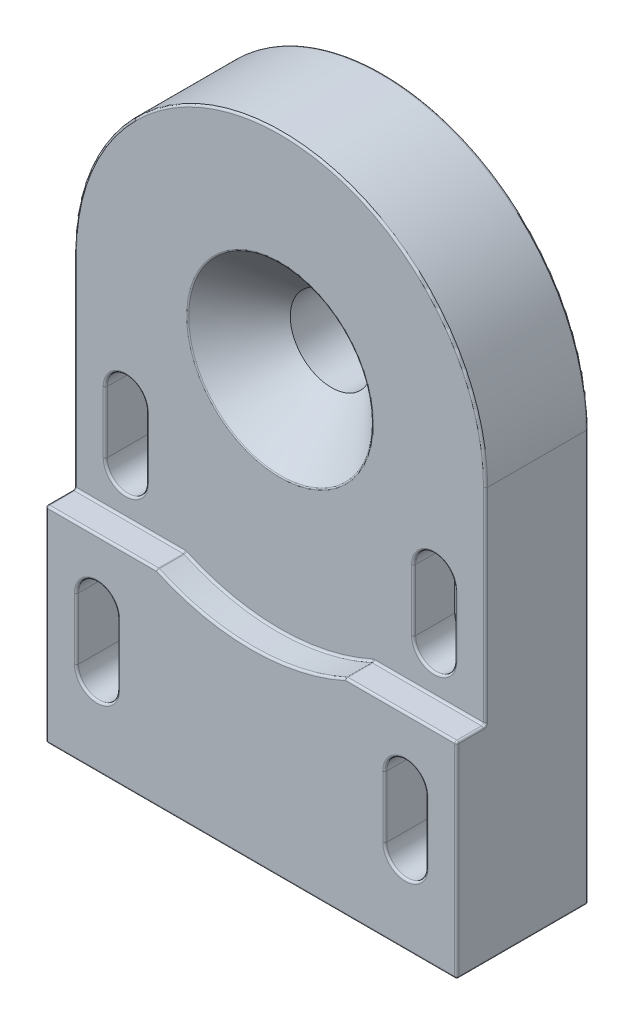
SolidWorks part; units mm, degrees
ref_plane "Front Plane" through (0, 0, 0) normal (0, 0, 1) x (1, 0, 0)
ref_plane "Top Plane" through (0, 0, 0) normal (0, 1, 0) x (1, 0, 0)
ref_plane "Right Plane" through (0, 0, 0) normal (1, 0, 0) x (0, 0, -1)
sketch "Sketch1" plane through (0, 0, 0) normal (0, 0, 1) x (1, 0, 0)
  line L0 (-7.5, -13) -> (-7.5, -16) construction
  line L1 (-10, -20) -> (10, -20)
  line L2 (-10, -20) -> (-10, 10)
  line L4 (10, -20) -> (10, 10)
  line L5 (-6.5, -13) -> (-6.5, -16)
  line L6 (-8.5, -13) -> (-8.5, -16)
  line L7 (0, 10) -> (0, -20) construction
  line L8 (7.5, -13) -> (7.5, -16) construction
  line L11 (6.5, -13) -> (6.5, -16)
  line L12 (8.5, -13) -> (8.5, -16)
  line L23 (-10, 10) -> (10, 10)
  line L24 (-8.5, -5) -> (-8.5, -8)
  line L29 (-6.5, -5) -> (-6.5, -8)
  line L30 (6.5, -5) -> (6.5, -8)
  line L31 (8.5, -5) -> (8.5, -8)
  line L32 (-7.5, -5) -> (-7.5, -8) construction
  line L33 (7.5, -5) -> (7.5, -8) construction
  circle A1 centre (0, 0) radius 2
  arc A2 (-6.5, -13) -> (-8.5, -13) centre (-7.5, -13) ccw
  arc A3 (-8.5, -16) -> (-6.5, -16) centre (-7.5, -16) ccw
  arc A6 (6.5, -13) -> (8.5, -13) centre (7.5, -13) cw
  arc A7 (8.5, -16) -> (6.5, -16) centre (7.5, -16) cw
  arc A8 (-6.5, -5) -> (-8.5, -5) centre (-7.5, -5) ccw
  arc A9 (-8.5, -8) -> (-6.5, -8) centre (-7.5, -8) ccw
  arc A10 (8.5, -8) -> (6.5, -8) centre (7.5, -8) cw
  arc A11 (6.5, -5) -> (8.5, -5) centre (7.5, -5) cw
  point P0 (0, 0)
  point P10 (-7.5, -14.5)
  point P16 (-7.5, -12)
  point P17 (-7.5, -17)
  point P19 (7.5, -14.5)
  point P25 (7, 0.509)
  point P26 (-7.5, -6.5)
  point P36 (7.5, -6.5)
  dimension "D1" = 4
  dimension "D6" = 5
  dimension "D2" = 20
  dimension "D3" = 30
  dimension "D4" = 20
  dimension "D5" = 2
  dimension "D7" = 1.5
  dimension "D8" = 4
  dimension "D9" = 10
  dimension "D10" = 2
  dimension "D11" = 8
extrude "Boss-Extrude1" add sketch "Sketch1" along normal blind 5
chamfer "Chamfer1" distance 2.5 angle 45 1 edges at (2, 0, 5)
sketch "Sketch2" plane through (0, 0, 5) normal (0, 0, 1) x (1, 0, 0)
  line L0 (10, -20) -> (10, 10) construction
  line L1 (-10, -20) -> (10, -20)
  line L2 (-10, -20) -> (-10, -10)
  line L3 (-10, -10) -> (-4.5826, -10)
  line L4 (10, -20) -> (10, -10)
  line L7 (-8.5, -13) -> (-8.5, -16) construction
  line L8 (-6.5, -16) -> (-6.5, -13) construction
  line L11 (-8.5, -13) -> (-8.5, -16)
  line L12 (-6.5, -16) -> (-6.5, -13)
  line L13 (4.5826, -10) -> (10, -10)
  line L14 (8.5, -16) -> (8.5, -13) construction
  line L15 (6.5, -13) -> (6.5, -16) construction
  line L16 (8.5, -16) -> (8.5, -13)
  line L17 (6.5, -13) -> (6.5, -16)
  arc A2 (-8.5, -16) -> (-6.5, -16) centre (-7.5, -16) ccw construction
  arc A3 (-6.5, -13) -> (-8.5, -13) centre (-7.5, -13) ccw construction
  arc A6 (-8.5, -16) -> (-6.5, -16) centre (-7.5, -16) ccw
  arc A7 (-6.5, -13) -> (-8.5, -13) centre (-7.5, -13) ccw
  arc A9 (-4.5826, -10) -> (4.5826, -10) centre (0, 0) ccw
  arc A10 (6.5, -16) -> (8.5, -16) centre (7.5, -16) ccw construction
  arc A11 (8.5, -13) -> (6.5, -13) centre (7.5, -13) ccw construction
  arc A12 (6.5, -16) -> (8.5, -16) centre (7.5, -16) ccw
  arc A13 (8.5, -13) -> (6.5, -13) centre (7.5, -13) ccw
  circle A14 centre (0, 0) radius 4.5 construction
  point P10 (0, -2)
  point P15 (0, 0)
  point P28 (0, -11)
  dimension "D2" = 1
  dimension "D1" = 10
extrude "Boss-Extrude2" add sketch "Sketch2" along normal blind 1.4
sketch "Sketch3" plane through (0, 0, 0) normal (0, 0, -1) x (-1, 0, 0)
  line L0 (-7.5, -12) -> (7.5, -12)
  line L1 (7.5, -17) -> (-7.5, -17)
  line L2 (8.5, -13) -> (8.5, -16) construction
  line L4 (8.5, -13) -> (8.5, -16)
  line L6 (-8.5, -16) -> (-8.5, -13) construction
  line L7 (-8.5, -16) -> (-8.5, -13)
  line L8 (-8.5, -8) -> (-8.5, -5)
  line L9 (-7.5, -4) -> (7.5, -4)
  line L10 (8.5, -5) -> (8.5, -8)
  line L11 (7.5, -9) -> (-7.5, -9)
  arc A0 (-7.5, -4) -> (-8.5, -5) centre (-7.5, -5) ccw
  arc A1 (8.5, -13) -> (6.5, -13) centre (7.5, -13) ccw construction
  arc A2 (6.5, -16) -> (8.5, -16) centre (7.5, -16) ccw construction
  arc A3 (8.5, -5) -> (7.5, -4) centre (7.5, -5) ccw
  arc A4 (8.5, -13) -> (7.5, -12) centre (7.5, -13) ccw
  arc A5 (7.5, -17) -> (8.5, -16) centre (7.5, -16) ccw
  arc A8 (-8.5, -16) -> (-6.5, -16) centre (-7.5, -16) ccw construction
  arc A9 (-6.5, -13) -> (-8.5, -13) centre (-7.5, -13) ccw construction
  arc A10 (-8.5, -16) -> (-7.5, -17) centre (-7.5, -16) ccw
  arc A11 (-7.5, -12) -> (-8.5, -13) centre (-7.5, -13) ccw
  arc A12 (7.5, -9) -> (8.5, -8) centre (7.5, -8) ccw
  arc A13 (-8.5, -8) -> (-7.5, -9) centre (-7.5, -8) ccw
  arc A15 (-6.5, -5) -> (-8.5, -5) centre (-7.5, -5) ccw construction
  dimension "D1" = 2
extrude "Cut-Extrude1" cut sketch "Sketch3" against normal blind 3
chamfer "Chamfer2" distance 0.5 angle 45 4 edges at (0, -17, 3) (0, -12, 3) (0, -9, 3) (0, -4, 3)
sketch "Sketch4" plane through (0, 0, 0) normal (1, 0, 0) x (0, 0, -1)
  line L0 (-5, 12) -> (-5, 14)
  line L2 (-3, 10) -> (0, 10)
  line L3 (0, 10) -> (0, 13)
  line L4 (0, 13) -> (-5, 14)
  line L5 (-5, -10) -> (-5, 10) construction
  line L8 (-5, 12) -> (-3, 12)
  line L9 (-3, 10) -> (-3, 12)
  point P3 (0, 8.8485)
  point P8 (-5, 13)
  point P12 (0, 9)
  point P13 (-4.3259, 10)
  dimension "D1" = 4
  dimension "D2" = 2
extrude "Boss-Extrude3" [suppressed] add sketch "Sketch4" along normal mid plane 3
sketch "Sketch5" [suppressed] plane through (0, 0, 5) normal (0, 0, 1) x (1, 0, 0)
  line L0 (1.5, 10) -> (1.5, 8) construction
  line L1 (-1.5, 10) -> (1.5, 10)
  line L2 (-1.5, 10) -> (-1.5, 7)
  line L3 (-1.5, 7) -> (1.5, 7)
  line L4 (1.5, 10) -> (1.5, 7)
  point P7 (0, 0)
  dimension "D1" = 3
extrude "Boss-Extrude4" [suppressed] add sketch "Sketch5" along normal blind 2
sketch "Sketch6" plane through (0, 0, 5) normal (0, 0, 1) x (1, 0, 0)
  line L3 (-10, 10) -> (-10, -10) construction
  line L4 (10, 10) -> (-10, 10)
  line L5 (-10, 10) -> (-10, 0)
  line L6 (0, -55) -> (0, 55) construction
  line L7 (10, 10) -> (10, 0)
  arc A0 (10, 0) -> (-10, 0) centre (0, 0) ccw
  circle A3 centre (0, 0) radius 4.5 construction
  circle A4 centre (0, 0) radius 4.5 construction
  line M5 (10, -10) -> (10, 10)
  line M6 (10, 10) -> (-10, 10)
  line M7 (-10, 10) -> (-10, -10)
extrude "Cut-Extrude2" cut sketch "Sketch6" against normal through all contours A0 L4 M7 | A0 M5 M6 region at (7.7663, 7.7663, 5) region at (-7.7663, 7.7663, 5)
fillet "Fillet1" radius 0.1 39 edges at (0, 10, 0) (0, 10, 5) (7.5, -9, 5) (8.5, -6.5, 5) (7.5, -4, 5) (6.5, -6.5, 5) (-7.5, -9, 5) (-6.5, -6.5, 5) (-7.5, -4, 5) (-8.5, -6.5, 5) (4.5, 0, 5) (-7.5, -12, 6.4) (-8.5, -14.5, 6.4) (-7.5, -17, 6.4) (-6.5, -14.5, 6.4) (7.5, -12, 6.4) (6.5, -14.5, 6.4) (7.5, -17, 6.4) (8.5, -14.5, 6.4) (7.2913, -10, 6.4) (7.2913, -10, 5) (-7.2913, -10, 6.4) (-7.2913, -10, 5) (4.5826, -10, 5.7) (0, -11, 6.4) (-4.5826, -10, 5.7) (0, -11, 5) (-10, -5, 5) (-10, -10, 5.7) (-10, -15, 6.4) (-10, -10, 0) (10, -15, 6.4) (10, -10, 5.7) (10, -5, 5) (10, -10, 0) (-10, -20, 3.2) (0, -20, 6.4) (10, -20, 3.2) (0, -20, 0)
